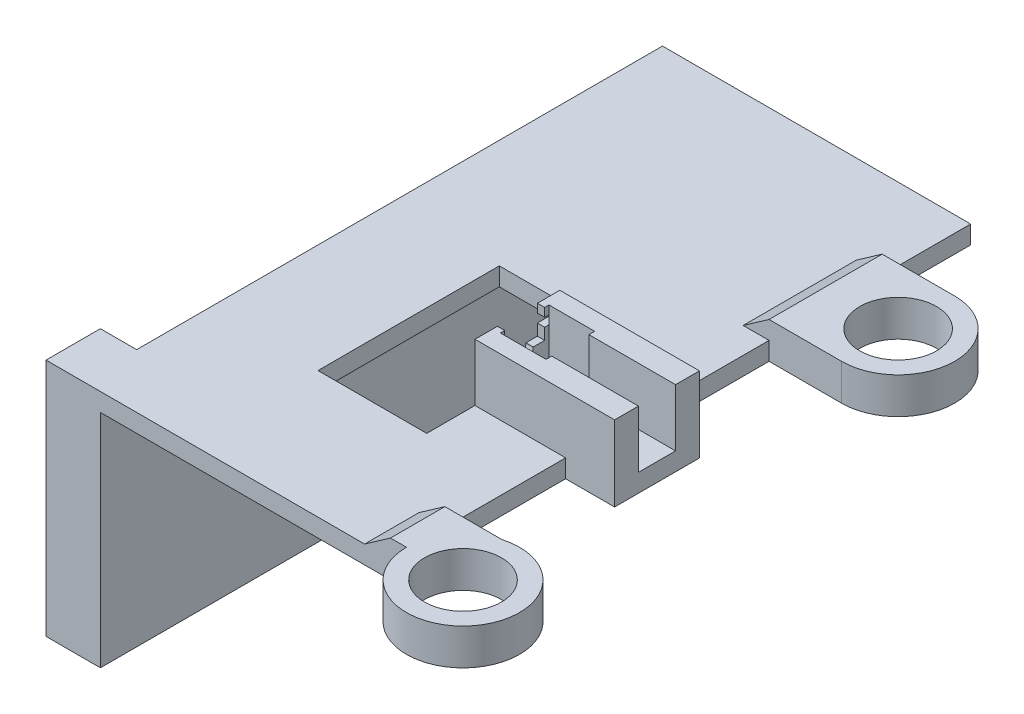
SolidWorks part; units mm, degrees
ref_plane "Front Plane" through (0, 0, 0) normal (0, 0, 1) x (1, 0, 0)
ref_plane "Top Plane" through (0, 0, 0) normal (0, 1, 0) x (1, 0, 0)
ref_plane "Right Plane" through (0, 0, 0) normal (1, 0, 0) x (0, 0, -1)
sketch "Sketch1" plane through (0, 0, 0) normal (0, 1, 0) x (1, 0, 0)
  line L1 (-50.8, -76.2) -> (50.8, -76.2)
  line L2 (-50.8, -76.2) -> (-50.8, 76.2)
  line L3 (-50.8, 76.2) -> (50.8, 76.2)
  line L4 (50.8, -76.2) -> (50.8, 76.2)
  line L5 (-50.8, -76.2) -> (50.8, 76.2) construction
  line L6 (-50.8, 76.2) -> (50.8, -76.2) construction
  point P0 (0, 0)
  dimension "D1" = 152.4
  dimension "D2" = 101.6
extrude "Boss-Extrude1" add sketch "Sketch1" against normal blind 6.35
sketch "Sketch2" plane through (0, 0, 0) normal (0, 1, 0) x (1, 0, 0)
  line L1 (-19.05, -31.75) -> (19.05, -31.75)
  line L2 (-19.05, -31.75) -> (-19.05, 31.75)
  line L3 (-19.05, 31.75) -> (19.05, 31.75)
  line L4 (19.05, -31.75) -> (19.05, 31.75)
  line L5 (-19.05, -31.75) -> (19.05, 31.75) construction
  line L6 (-19.05, 31.75) -> (19.05, -31.75) construction
  point P0 (0, 0)
  dimension "D1" = 38.1
  dimension "D2" = 63.5
extrude "Cut-Extrude1" cut sketch "Sketch2" against normal through all
sketch "Sketch4" plane through (0, 0, 0) normal (0, 1, 0) x (1, 0, 0)
  line L0 (19.05, -31.75) -> (19.05, 31.75) construction
  line L1 (21.59, -8.509) -> (50.8, -8.509)
  line L3 (21.59, 8.509) -> (50.8, 8.509)
  line L4 (50.8, -8.509) -> (50.8, 8.509)
  line L5 (21.59, -8.509) -> (50.8, 8.509) construction
  line L6 (50.8, -8.509) -> (21.59, 8.509) construction
  line L7 (50.8, -76.2) -> (50.8, 76.2) construction
  line L9 (19.05, 14.859) -> (19.05, -14.859)
  line L10 (19.05, 14.859) -> (50.8, 14.859)
  line L11 (50.8, 14.859) -> (50.8, 8.509)
  line L12 (21.59, 8.509) -> (21.59, -8.509)
  line L13 (50.8, 8.509) -> (61.595, 8.509)
  line L14 (19.05, -14.859) -> (50.8, -14.859)
  line L15 (61.595, 8.509) -> (61.595, -8.509)
  line L16 (61.595, -8.509) -> (50.8, -8.509)
  line L17 (50.8, 14.859) -> (67.945, 14.859)
  line L18 (67.945, 14.859) -> (67.945, -14.859)
  line L19 (67.945, -14.859) -> (50.8, -14.859)
  point P0 (19.05, 0)
  point P2 (36.195, 0)
  line M13 (19.05, 31.75) -> (19.05, -31.75)
  line M16 (50.8, -76.2) -> (50.8, 76.2)
  dimension "D1" = 17.018
  dimension "D2" = 6.35
  dimension "D3" = 6.35
  dimension "D4" = 2.54
  dimension "D5" = 40.005
  dimension "D6" = 6.35
extrude "Boss-Extrude3" add sketch "Sketch4" against normal through all and the other way blind 10.0965 contours L19 L18 L17 L13 L15 L16 M16 | L14 L1 L12 L3 L10 M13 M16 region at (36.195, 0, 8.9439) region at (56.1975, 0, 8.8521)
sketch "Sketch6" plane through (19.05, 0, 0) normal (-1, 0, 0) x (0, 0, 1)
  line L0 (-14.859, 10.0965) -> (14.859, 10.0965) construction
  circle A0 centre (0, 10.0965) radius 3
  dimension "D1" = 6
extrude "Cut-Extrude2" cut sketch "Sketch6" against normal up to next
sketch "Sketch7" plane through (0, 10.0965, 0) normal (0, 1, 0) x (1, 0, 0)
  line L0 (21.59, 8.509) -> (37.59, 8.509) construction
  line L1 (21.59, 8.509) -> (61.595, 8.509) construction
  line L2 (37.59, 8.509) -> (37.59, 6.5)
  line L3 (37.59, 6.5) -> (61.595, 6.5)
  line L4 (61.595, 8.509) -> (61.595, -8.509) construction
  line L5 (61.595, 6.5) -> (61.595, -6.5)
  line L6 (61.595, -6.5) -> (37.59, -6.5)
  line L7 (37.59, -6.5) -> (37.59, -8.509)
  line L8 (61.595, -8.509) -> (21.59, -8.509) construction
  line L9 (37.59, -8.509) -> (61.595, -8.509)
  line L10 (61.595, -8.509) -> (61.595, -6.5)
  line L11 (61.595, 6.5) -> (61.595, 8.509)
  line L12 (61.595, 8.509) -> (37.59, 8.509)
  line L13 (21.59, 8.509) -> (21.59, 3) construction
  line M8 (21.59, 8.509) -> (61.595, 8.509)
  line M9 (61.595, 8.509) -> (61.595, -8.509)
  dimension "D1" = 13
  dimension "D2" = 16
  dimension "D3" = 24.005
extrude "Boss-Extrude4" add sketch "Sketch7" against normal through all contours L2 L3 M9 M8 | L6 L7 L9 L10 region at (49.5925, 10.0965, -7.5045)
sketch "Sketch10" plane through (50.8, 0, 0) normal (1, 0, 0) x (0, 0, -1)
  line L1 (-6.5, -6.35) -> (6.5, -6.35)
  line L2 (-6.5, -6.35) -> (-6.5, 0)
  line L3 (-6.5, 0) -> (6.5, 0)
  line L4 (6.5, -6.35) -> (6.5, 0)
extrude "Boss-Extrude5" add sketch "Sketch10" along normal through all
sketch "Sketch11" plane through (61.595, 0, 0) normal (-1, 0, 0) x (0, 0, 1)
  line L1 (6.5, 0) -> (-6.5, 0)
  line L2 (6.5, 0) -> (6.5, 10.0965)
  line L3 (6.5, 10.0965) -> (-6.5, 10.0965)
  line L4 (-6.5, 0) -> (-6.5, 10.0965)
extrude "Cut-Extrude3" cut sketch "Sketch11" against normal up to next
sketch "Sketch12" plane through (0, 10.0965, 0) normal (0, 1, 0) x (1, 0, 0)
  line L0 (67.945, -14.859) -> (67.945, -6.5) construction
  line L1 (67.945, -6.5) -> (37.59, -6.5) construction
  line L2 (37.59, -6.5) -> (37.59, -8.509) construction
  line L3 (37.59, -8.509) -> (21.59, -8.509) construction
  line L4 (21.59, -8.509) -> (21.59, -3) construction
  line L5 (21.59, -3) -> (19.05, -3) construction
  line L6 (19.05, -3) -> (19.05, -14.859) construction
  line L7 (19.05, -14.859) -> (67.945, -14.859) construction
  line L8 (37.59, 6.5) -> (67.945, 6.5) construction
  line L9 (67.945, 6.5) -> (67.945, 14.859) construction
  line L10 (67.945, 14.859) -> (19.05, 14.859) construction
  line L11 (19.05, 14.859) -> (19.05, 3) construction
  line L12 (19.05, 3) -> (21.59, 3) construction
  line L13 (21.59, 3) -> (21.59, 8.509) construction
  line L14 (21.59, 8.509) -> (37.59, 8.509) construction
  line L15 (37.59, 8.509) -> (37.59, 6.5) construction
  line L16 (67.945, -14.859) -> (67.945, -6.5)
  line L17 (67.945, -6.5) -> (37.59, -6.5)
  line L18 (37.59, -6.5) -> (37.59, -8.509)
  line L19 (37.59, -8.509) -> (21.59, -8.509)
  line L20 (21.59, -8.509) -> (21.59, -3)
  line L21 (21.59, -3) -> (19.05, -3)
  line L22 (19.05, -3) -> (19.05, -14.859)
  line L23 (19.05, -14.859) -> (67.945, -14.859)
  line L24 (37.59, 6.5) -> (67.945, 6.5)
  line L25 (67.945, 6.5) -> (67.945, 14.859)
  line L26 (67.945, 14.859) -> (19.05, 14.859)
  line L27 (19.05, 14.859) -> (19.05, 3)
  line L28 (19.05, 3) -> (21.59, 3)
  line L29 (21.59, 3) -> (21.59, 8.509)
  line L30 (21.59, 8.509) -> (37.59, 8.509)
  line L31 (37.59, 8.509) -> (37.59, 6.5)
extrude "Boss-Extrude6" add sketch "Sketch12" along normal blind 10
sketch "Sketch13" plane through (19.05, 0, 0) normal (-1, 0, 0) x (0, 0, 1)
  line L0 (3, 10.0965) -> (7, 10.0965)
  line L1 (7, 10.0965) -> (7, 14.0965)
  line L2 (7, 14.0965) -> (11, 14.0965)
  line L3 (11, 14.0965) -> (11, 17.0965)
  line L4 (11, 17.0965) -> (7, 17.0965)
  line L5 (7, 17.0965) -> (7, 20.0965)
  line L6 (3, 20.0965) -> (14.859, 20.0965) construction
  line L7 (7, 20.0965) -> (3, 20.0965)
  line L8 (3, 20.0965) -> (3, 10.0965)
  arc A0 (-3, 10.0965) -> (3, 10.0965) centre (0, 10.0965) ccw construction
  arc A1 (-3, 10.0965) -> (3, 10.0965) centre (0, 10.0965) ccw construction
  dimension "D1" = 4
  dimension "D2" = 4
  dimension "D3" = 3
  dimension "D4" = 4
extrude "Cut-Extrude4" cut sketch "Sketch13" against normal up to surface (2.54 mm away)
mirror "Mirror1" about plane through (0, 0, 0) normal (0, 0, 1) of "Cut-Extrude4"
sketch "Sketch14" plane through (0, 0, -76.2) normal (0, 0, -1) x (-1, 0, 0)
  line L4 (50.8, 0) -> (-50.8, 0)
  line L5 (-50.8, 0) -> (-50.8, -6.35)
  line L6 (-50.8, -6.35) -> (50.8, -6.35)
  line L7 (50.8, -6.35) -> (50.8, 0)
  line L8 (50.8, 0) -> (-50.8, 0)
  line L9 (-50.8, 0) -> (-50.8, -6.35)
  line L10 (-50.8, -6.35) -> (50.8, -6.35)
  line L11 (50.8, -6.35) -> (50.8, 0)
  dimension "D1" = 0
extrude "Boss-Extrude7" add sketch "Sketch14" along normal blind 50.8
sketch "Sketch15" plane through (0, -6.35, 0) normal (0, -1, 0) x (1, 0, 0)
  line L1 (-69.85, 76.2) -> (-50.8, 76.2)
  line L2 (-69.85, 76.2) -> (-69.85, 57.15)
  line L3 (-69.85, 57.15) -> (-50.8, 57.15)
  line L4 (-50.8, 76.2) -> (-50.8, 57.15)
  line L9 (-50.8, -127) -> (-31.75, -127)
  line L10 (-50.8, -127) -> (-50.8, -107.95)
  line L11 (-50.8, -107.95) -> (-31.75, -107.95)
  line L12 (-31.75, -127) -> (-31.75, -107.95)
  dimension "D1" = 19.05
  dimension "D2" = 19.05
  dimension "D3" = 19.05
extrude "Boss-Extrude8" add sketch "Sketch15" along normal blind 77.47
sketch "Sketch16" plane through (0, -6.35, 0) normal (0, 1, 0) x (1, 0, 0)
  line L4 (-69.85, -57.15) -> (-69.85, -76.2) construction
  line L5 (-69.85, -76.2) -> (-50.8, -76.2) construction
  line L6 (-50.8, -76.2) -> (-50.8, -57.15) construction
  line L7 (-50.8, -57.15) -> (-69.85, -57.15) construction
  line L12 (-69.85, -57.15) -> (-69.85, -76.2)
  line L13 (-69.85, -76.2) -> (-50.8, -76.2)
  line L14 (-50.8, -76.2) -> (-50.8, -57.15)
  line L15 (-50.8, -57.15) -> (-69.85, -57.15)
extrude "Boss-Extrude9" add sketch "Sketch16" along normal up to surface (6.35 mm away) up to face at (11.6417, 0, -8.4667)
sketch "Sketch17" plane through (-50.8, 0, 0) normal (-1, 0, 0) x (0, 0, 1)
  line L1 (-127, 0) -> (57.15, 0)
  line L2 (-127, 0) -> (-127, -83.82)
  line L3 (-127, -83.82) -> (57.15, -83.82)
  line L4 (57.15, 0) -> (57.15, -83.82)
extrude "Boss-Extrude10" add sketch "Sketch17" along normal blind 6.35
sketch "Sketch18" plane through (0, 0, 0) normal (0, 1, 0) x (1, 0, 0)
  line L0 (50.8, -76.2) -> (-69.85, -76.2) construction
  line L1 (0, 0) -> (76.2, 76.2) construction
  line L2 (-76.2, -76.2) -> (76.2, -76.2) construction
  line L3 (0, 0) -> (76.2, -76.2) construction
  line L4 (76.2, 96.012) -> (50.8, 96.012)
  line L5 (50.8, 14.859) -> (50.8, 127) construction
  line L6 (76.2, 56.388) -> (50.8, 56.388)
  line L7 (50.8, 96.012) -> (50.8, 56.388)
  circle A1 centre (76.2, -76.2) radius 13.462
  circle A2 centre (76.2, 76.2) radius 13.462
  arc A3 (76.2, 56.388) -> (76.2, 96.012) centre (76.2, 76.2) ccw
  circle A4 centre (76.2, -76.2) radius 19.812
  circle A5 centre (76.2, 76.2) radius 19.812 construction
  dimension "D1" = 152.4
  dimension "D2" = 26.924
  dimension "D3" = 6.35
extrude "Boss-Extrude11" add sketch "Sketch18" along normal blind 6.35 and the other way blind 6.35
sketch "Sketch21" plane through (0, 6.35, 0) normal (0, 1, 0) x (1, 0, 0)
  line L0 (56.388, -76.2) -> (50.8, -76.2)
  line L1 (50.8, -76.2) -> (50.8, -57.15)
  line L2 (50.8, -76.2) -> (50.8, -14.859) construction
  line L3 (50.8, -57.15) -> (70.7582, -57.15)
  line L4 (76.2, 96.012) -> (50.8, 96.012) construction
  line L5 (50.8, 56.388) -> (58.42, 56.388)
  line L6 (50.8, 56.388) -> (50.8, 96.012)
  line L7 (50.8, 96.012) -> (58.42, 96.012)
  line L8 (58.42, 56.388) -> (58.42, 96.012)
  circle A1 centre (76.2, -76.2) radius 19.812 construction
  arc A3 (70.7582, -57.15) -> (56.388, -76.2) centre (76.2, -76.2) ccw
  dimension "D1" = 7.62
  dimension "D2" = 19.05
extrude "Boss-Extrude13" add sketch "Sketch21" against normal up to surface (12.7 mm away) up to face at (0, -6.35, 0)
chamfer "Chamfer1" distance 6.35 angle 55 2 edges at (50.8, 0, 66.675) (50.8, 0, -76.2) first distance on face at (50.8, 3.175, 66.675) first distance on face at (50.8, 3.175, -76.2)
